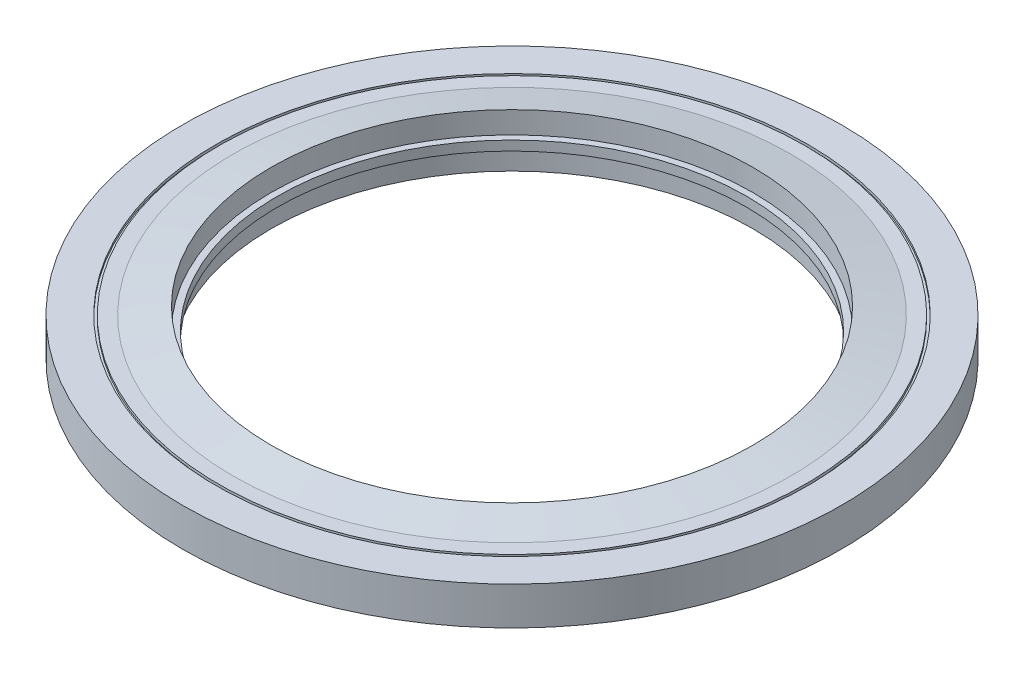
SolidWorks part; units mm, degrees
ref_plane "Front Plane" through (0, 0, 0) normal (0, 0, 1) x (1, 0, 0)
ref_plane "Top Plane" through (0, 0, 0) normal (0, 1, 0) x (1, 0, 0)
ref_plane "Right Plane" through (0, 0, 0) normal (1, 0, 0) x (0, 0, -1)
sketch "Sketch1" plane through (0, 0, 0) normal (0, 0, 1) x (1, 0, 0)
  line L0 (0, 0) -> (0, 5.1453) construction
  line L1 (9.25, -0.1875) -> (9.25, 0.1875)
  line L2 (9.25, -0.1875) -> (11, -0.75) construction
  line L3 (11, -0.75) -> (11.5667, -0.75)
  line L4 (11.6667, -0.75) -> (13, -0.75)
  line L5 (13, -0.75) -> (13, 0.75)
  line L6 (13, 0.75) -> (11.6667, 0.75)
  line L7 (16.6173, 0) -> (-12.4517, 0) construction
  line L8 (11, 0.75) -> (11.5667, 0.75)
  line L9 (9.25, 0.1875) -> (11, 0.75) construction
  line L10 (11.6667, 0.75) -> (11.6667, 0.65)
  line L11 (11.6667, 0.65) -> (11.5667, 0.65)
  line L12 (11.5667, 0.65) -> (11.5667, 0.75)
  line L13 (11.5667, -0.65) -> (11.5667, -0.75)
  line L14 (11.6667, -0.65) -> (11.5667, -0.65)
  line L15 (11.6667, -0.75) -> (11.6667, -0.65)
  line L16 (11, 0.75) -> (9.5, 1.05)
  line L17 (9.5, 1.05) -> (9.5, 0.1875)
  line L18 (9.25, 0.1875) -> (9.5, 0.1875)
  line L19 (9.25, -0.1875) -> (9.5, -0.1875)
  line L20 (9.5, -1.05) -> (9.5, -0.1875)
  line L21 (11, -0.75) -> (9.5, -1.05)
  point P15 (9.25, 0)
  dimension "OD" = 26
  dimension "C" = 18.5
  dimension "d1" = 22
  dimension "S" = 1.5
  dimension "E" = 0.375
  dimension "D2" = 0.1
  dimension "D3" = 0.1
  dimension "D4" = 23.3333
  dimension "P" = 0.3
  dimension "d" = 19
revolve "Revolve1" add sketch "Sketch1" angle 360 about L0
ref_axis "Axis1" through (0, 1.43, 0) along (0, -1, 0)
sketch "Sketch2" plane through (0, 0, 0) normal (0, 0, 1) x (1, 0, 0)
  line L0 (0, 0) -> (0, -4.6258) construction
  line L1 (11.6667, 0.75) -> (13, 0.75)
  line L2 (11.6667, 0.75) -> (11.6667, -0.75)
  line L3 (11.6667, -0.75) -> (13, -0.75)
  line L4 (13, 0.75) -> (13, -0.75)
  line L5 (0, 1.43) -> (0, -1.43) construction
revolve "Revolve2" [suppressed] add sketch "Sketch2" angle 360 about L0
equation "\"D4@Sketch1\"=\"d1@Sketch1\" + ( \"OD@Sketch1\" - \"d1@Sketch1\" ) / 3"
